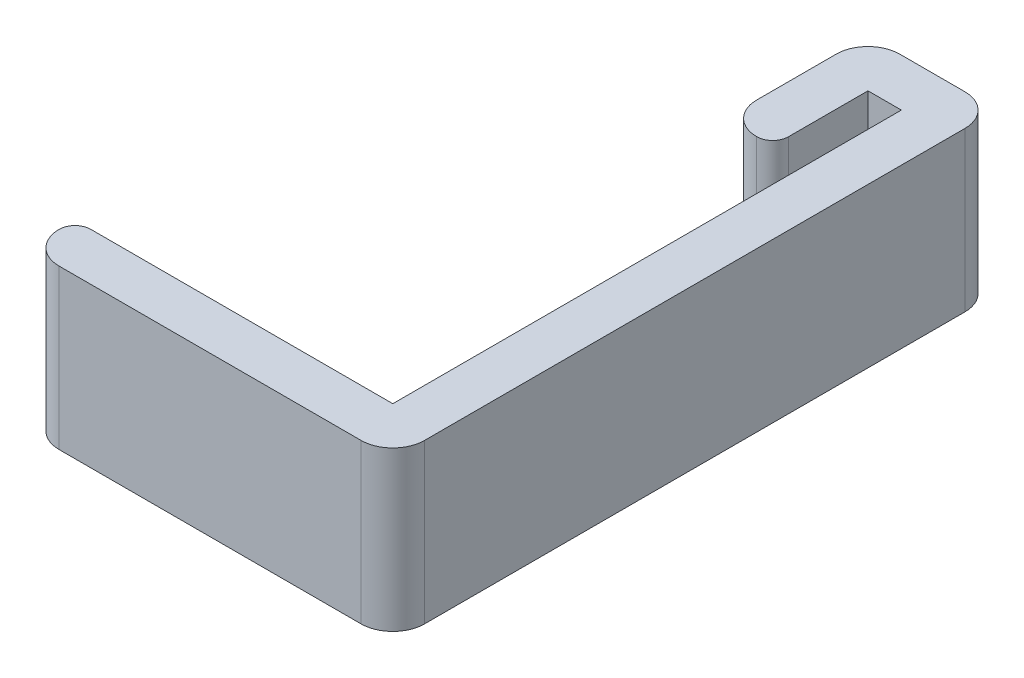
SolidWorks part; units mm, degrees
ref_plane "Front Plane" through (0, 0, 0) normal (0, 0, 1) x (1, 0, 0)
ref_plane "Top Plane" through (0, 0, 0) normal (0, 1, 0) x (1, 0, 0)
ref_plane "Right Plane" through (0, 0, 0) normal (1, 0, 0) x (0, 0, -1)
sketch "Sketch1" plane through (0, 0, 0) normal (0, 1, 0) x (1, 0, 0)
  line L0 (0, 0) -> (0, 6)
  line L1 (0, 6) -> (2.1, 6)
  line L2 (2.1, 6) -> (2.1, -26)
  line L3 (2.1, -26) -> (-17.9, -26)
  line L4 (-17.9, -29) -> (5.1, -29)
  line L5 (5.1, -29) -> (5.1, 9)
  line L6 (5.1, 9) -> (-3, 9)
  line L7 (-3, 9) -> (-3, 0)
  line L8 (-3, 0) -> (0, 0)
  line L9 (-17.9, -26) -> (-17.9, -29)
  dimension "D1" = 3
  dimension "D2" = 3
  dimension "D3" = 3
  dimension "D4" = 3
  dimension "D5" = 2.1
  dimension "D6" = 6
  dimension "D7" = 32
  dimension "D8" = 20
extrude "Boss-Extrude1" add sketch "Sketch1" along normal blind 10
fillet "Fillet1" radius 2 1 edges at (5.1, 5, -9)
fillet "Fillet2" radius 2 1 edges at (5.1, 5, 29)
fillet "Fillet3" radius 2 1 edges at (-17.9, 5, 29)
fillet "Fillet4" radius 2 1 edges at (-3, 5, -9)
fillet "Fillet5" radius 1 3 edges at (-17.9, 0, 26.5) (-17.9, 5, 26) (-17.9, 10, 26.5)
fillet "Fillet6" radius 2 1 edges at (-3, 5, 0)
fillet "Fillet7" radius 1 3 edges at (0, 5, 0) (-0.5, 0, 0) (-0.5, 10, 0)
